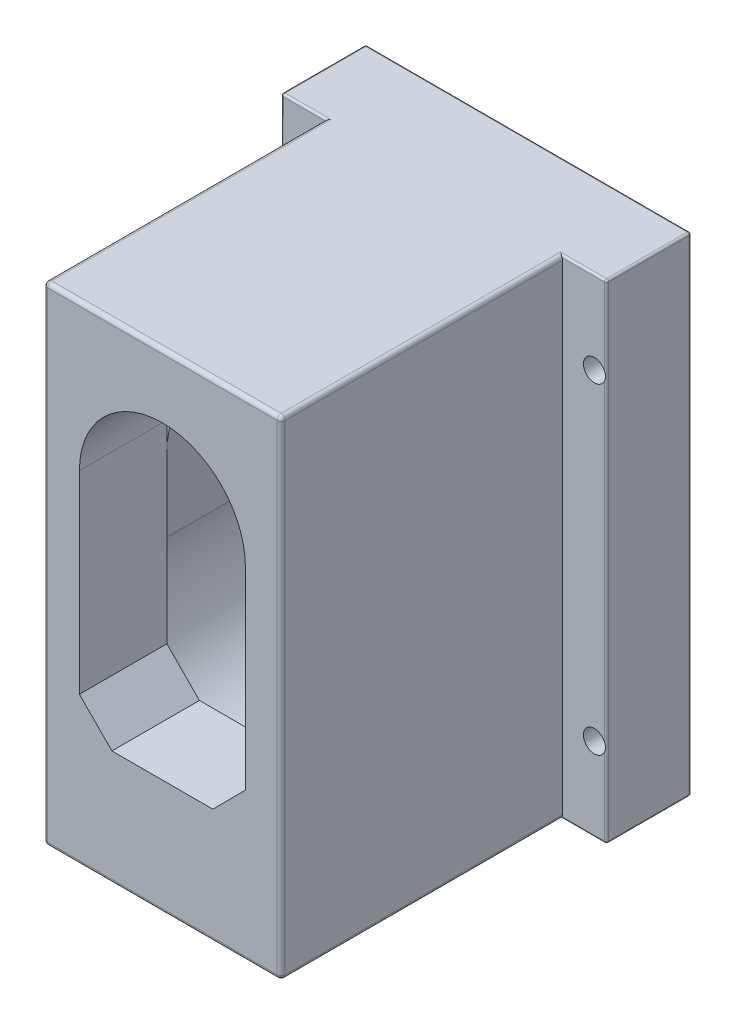
SolidWorks part; units mm, degrees
ref_plane "Plan de face" through (0, 0, 0) normal (0, 0, 1) x (1, 0, 0)
ref_plane "Plan de dessus" through (0, 0, 0) normal (0, 1, 0) x (1, 0, 0)
ref_plane "Plan de droite" through (0, 0, 0) normal (1, 0, 0) x (0, 0, -1)
sketch "Esquisse1" plane through (0, 0, 0) normal (0, 0, 1) x (1, 0, 0)
  line L0 (-4.8779, 36.0098) -> (-4.8779, -83.9902) construction
  line L1 (-44.8779, 36.0098) -> (35.1221, 36.0098)
  line L2 (-44.8779, 36.0098) -> (-44.8779, -83.9902)
  line L3 (-44.8779, -83.9902) -> (35.1221, -83.9902)
  line L4 (35.1221, 36.0098) -> (35.1221, -83.9902)
  dimension "D1" = 120
  dimension "D2" = 80
extrude "Boss.-Extru.1" add sketch "Esquisse1" along normal blind 90
sketch "Esquisse2" plane through (0, 0, 90) normal (0, 0, 1) x (1, 0, 0)
  line L0 (-4.8779, -83.9902) -> (-4.8779, 36.0098) construction
  line L1 (-44.8779, -83.9902) -> (35.1221, -83.9902) construction
  line L2 (35.1221, 36.0098) -> (-44.8779, 36.0098) construction
  line L3 (-25.2779, 0) -> (-25.2779, -47.6)
  line L4 (15.5221, 0) -> (15.5221, -47.6)
  line L5 (-4.8779, -55.6672) -> (7.5221, -55.6672)
  line L6 (-4.8779, -55.6672) -> (-17.2779, -55.6672)
  line L7 (15.5221, -47.6) -> (7.5221, -55.6672)
  line L8 (-25.2779, -47.6) -> (-17.2779, -55.6672)
  circle A0 centre (-4.8779, 0) radius 20.4
  dimension "D1" = 40.8
extrude "Enlèv. mat.-Extru.1" cut sketch "Esquisse2" against normal blind 21.5 contours L0 A0 | A0 L0 | L6 L0 A0 L3 L8 | L0 L5 L7 L4 A0 region at (-15.4139, -34.8603, 90) region at (5.6581, -34.8603, 90) region at (-13.5359, 0, 90) region at (3.7801, 0, 90)
sketch "Esquisse3" plane through (0, 0, 68.5) normal (0, 0, 1) x (1, 0, 0)
  line L0 (-25.2779, 0) -> (15.5221, 0) construction
  line L1 (-4.8779, 0) -> (-4.8779, -55.6672) construction
  line L2 (-17.2779, -55.6672) -> (7.5221, -55.6672) construction
  line L3 (-24.3779, 0) -> (-29.6983, -29.3249)
  line L4 (14.6221, 0) -> (19.9425, -29.3249)
  circle A0 centre (-4.8779, 0) radius 19.5
  circle A1 centre (-4.8779, -36.7247) radius 25.9
  line M3 (-25.2779, 0) -> (-25.2779, -47.6)
  line M4 (-25.2779, -47.6) -> (-17.2779, -55.6672)
  line M5 (-17.2779, -55.6672) -> (7.5221, -55.6672)
  line M6 (7.5221, -55.6672) -> (15.5221, -47.6)
  line M7 (15.5221, -47.6) -> (15.5221, 0)
  dimension "D1" = 39
  dimension "D2" = 51.8
extrude "Enlèv. mat.-Extru.7" cut sketch "Esquisse3" against normal through all contours A1 A0 | A1 A0 L3 M3 | A0 A1 | A1 L3 M3 | A1 A0 M7 M3 M4 M5 M6 | A1 M7 M6 M5 M4 M3 | A1 L4 A0 M7 | A1 L4 M7 region at (-23.1117, -12.3273, 68.5) region at (-4.8779, 2.2509, 68.5) region at (-26.6699, -17.7509, 68.5) region at (13.356, -12.3273, 68.5) region at (-4.8779, -15.0342, 68.5) region at (-4.8779, -35.9111, 68.5) region at (-27.2977, -25.1442, 68.5) region at (16.9142, -17.7509, 68.5)
sketch "Esquisse4" plane through (0, 36.0098, 0) normal (0, 1, 0) x (1, 0, 0)
  line L0 (-44.8779, -90) -> (-44.8779, 0) construction
  line L1 (-44.8779, -20.8) -> (-34.0779, -20.8)
  line L2 (-44.8779, -20.8) -> (-44.8779, -90)
  line L3 (-44.8779, -90) -> (-34.0779, -90)
  line L4 (-34.0779, -20.8) -> (-34.0779, -90)
  line L5 (35.1221, -90) -> (-44.8779, -90) construction
  line L6 (35.1221, -90) -> (35.1221, 0) construction
  line L7 (35.1221, -20.8) -> (24.3221, -20.8)
  line L8 (35.1221, -20.8) -> (35.1221, -90)
  line L9 (35.1221, -90) -> (24.3221, -90)
  line L10 (24.3221, -20.8) -> (24.3221, -90)
  line L11 (35.1221, 0) -> (-44.8779, 0) construction
  dimension "D1" = 20.8
  dimension "D2" = 20.8
  dimension "D3" = 10.8
  dimension "D4" = 10.8
extrude "Enlèv. mat.-Extru.8" cut sketch "Esquisse4" against normal through all
sketch "Esquisse5" plane through (0, 0, 0) normal (0, 0, -1) x (-1, 0, 0)
  line L0 (-32.1221, 15.5098) -> (41.8779, 15.5098) construction
  line L1 (-35.1221, -83.9902) -> (-35.1221, 36.0098) construction
  line L2 (44.8779, 36.0098) -> (44.8779, -83.9902) construction
  line L3 (-35.1221, 36.0098) -> (44.8779, 36.0098) construction
  line L4 (-32.1221, -63.4902) -> (41.8779, -63.4902) construction
  line L5 (44.8779, -83.9902) -> (-35.1221, -83.9902) construction
  circle A0 centre (-32.1221, -63.4902) radius 2.7
  circle A1 centre (41.8779, -63.4902) radius 2.7
  circle A2 centre (-32.1221, 15.5098) radius 2.7
  circle A3 centre (41.8779, 15.5098) radius 2.7
  dimension "D7" = 5.4
  dimension "D8" = 5.4
  dimension "D9" = 5.4
  dimension "D10" = 5.4
  dimension "D1" = 3
  dimension "D2" = 3
  dimension "D3" = 20.5
  dimension "D4" = 20.5
  dimension "D5" = 3
  dimension "D6" = 3
extrude "Enlèv. mat.-Extru.9" cut sketch "Esquisse5" against normal through all
fillet "Congé1" radius 0.5 4 edges at (35.1221, -23.9902, 0) (-4.8779, 36.0098, 0) (-4.8779, -83.9902, 0) (-44.8779, -23.9902, 0)
fillet "Congé2" radius 0.5 14 edges at (34.9757, 35.8634, 0.1464) (34.9757, -83.8437, 0.1464) (-44.7314, -83.8437, 0.1464) (-44.7314, 35.8634, 0.1464) (35.1221, 36.0098, 10.65) (29.7221, 36.0098, 20.8) (29.7221, -83.9902, 20.8) (35.1221, -83.9902, 10.65) (35.1221, -23.9902, 20.8) (-39.4779, -83.9902, 20.8) (-44.8779, -83.9902, 10.65) (-44.8779, -23.9902, 20.8) (-44.8779, 36.0098, 10.65) (-39.4779, 36.0098, 20.8)
fillet "Congé3" radius 1 8 edges at (-34.0779, -83.9902, 55.15) (24.3221, -83.9902, 55.15) (-4.8779, -83.9902, 90) (-34.0779, -23.9902, 90) (-4.8779, 36.0098, 90) (24.3221, -23.9902, 90) (-34.0779, 36.0098, 55.15) (24.3221, 36.0098, 55.15)
equation "\"0.5.00mm\"=10"
